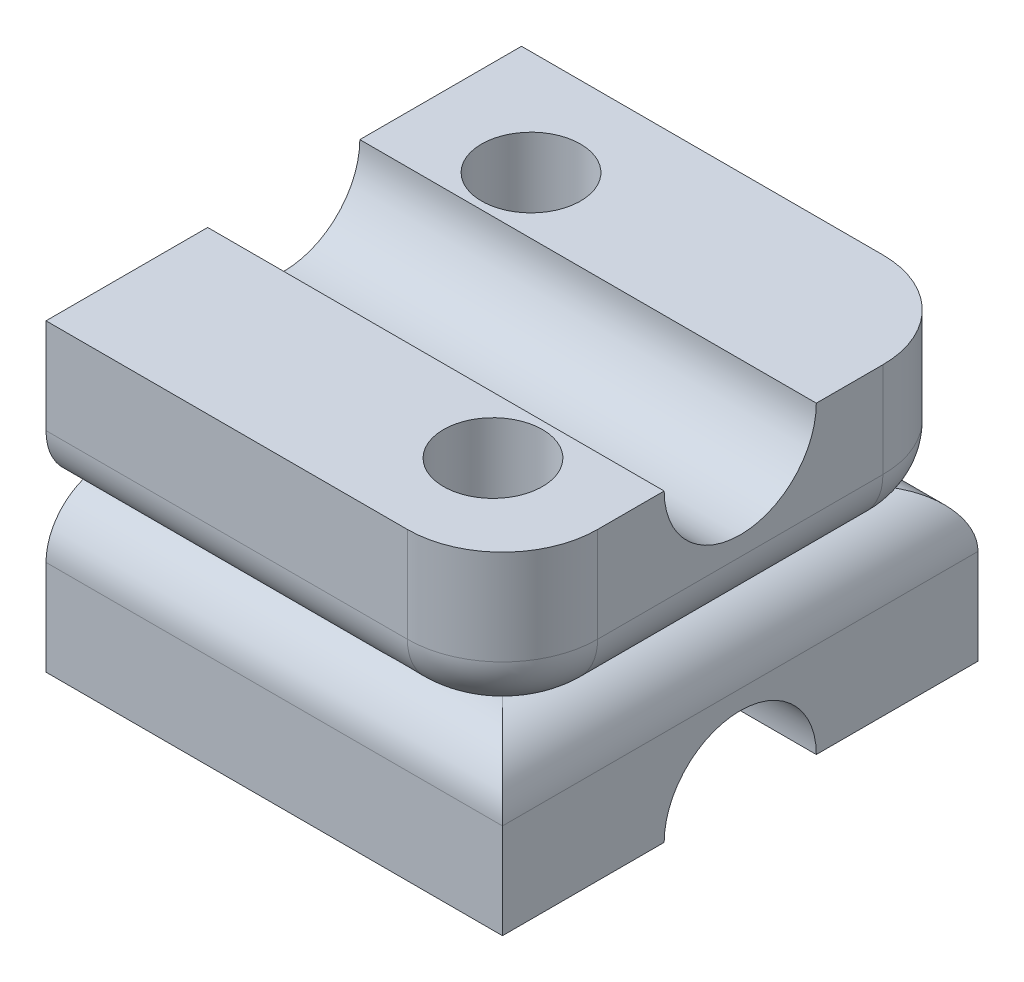
SolidWorks part; units mm, degrees
ref_plane "Front Plane" through (0, 0, 0) normal (0, 0, 1) x (1, 0, 0)
ref_plane "Top Plane" through (0, 0, 0) normal (0, 1, 0) x (1, 0, 0)
ref_plane "Right Plane" through (0, 0, 0) normal (1, 0, 0) x (0, 0, -1)
sketch "Sketch1" plane through (0, 0, 0) normal (0, 1, 0) x (1, 0, 0)
  line L1 (-12, 12.5) -> (12, 12.5)
  line L2 (-12, 12.5) -> (-12, -12.5)
  line L3 (-12, -12.5) -> (12, -12.5)
  line L4 (12, 12.5) -> (12, -12.5)
  line L5 (-12, 12.5) -> (12, -12.5) construction
  line L6 (-12, -12.5) -> (12, 12.5) construction
  point P0 (0, 0)
  dimension "D1" = 25
  dimension "D2" = 24
extrude "Boss-Extrude1" add sketch "Sketch1" along normal blind 8
sketch "Sketch2" plane through (-12, 0, 0) normal (-1, 0, 0) x (0, 0, 1)
  circle A0 centre (0, 0) radius 4
  dimension "D1" = 8
extrude "Cut-Extrude1" cut sketch "Sketch2" against normal through all
sketch "Sketch3" plane through (0, 0, 0) normal (0, -1, 0) x (1, 0, 0)
  line L0 (-6, -7) -> (6, 7) construction
  line L1 (-6, -7) -> (12.0808, -7) construction
  circle A0 centre (-6, -7) radius 2.6
  circle A1 centre (6, 7) radius 2.6
extrude "Cut-Extrude2" cut sketch "Sketch3" against normal through all
fillet "Fillet1" radius 3 3 edges at (0, 8, -12.5) (12, 8, 0) (0, 8, 12.5)
mirror "Mirror1" about plane through (0, 8, 0) normal (0, 1, 0) of bodies 103
fillet "Fillet2" radius 5 4 edges at (11.1213, 8.8787, 11.6213) (11.1213, 8.8787, -11.6213) (12, 13.5, -12.5) (12, 13.5, 12.5)
sketch "Sketch4" plane through (0, 8, 0) normal (0, -1, 0) x (1, 0, 0)
  circle A0 centre (-6, -7) radius 4.8
  circle A1 centre (6, 7) radius 4.8
  dimension "D1" = 9.6
extrude "Cut-Extrude3" cut sketch "Sketch4" against normal blind 4
